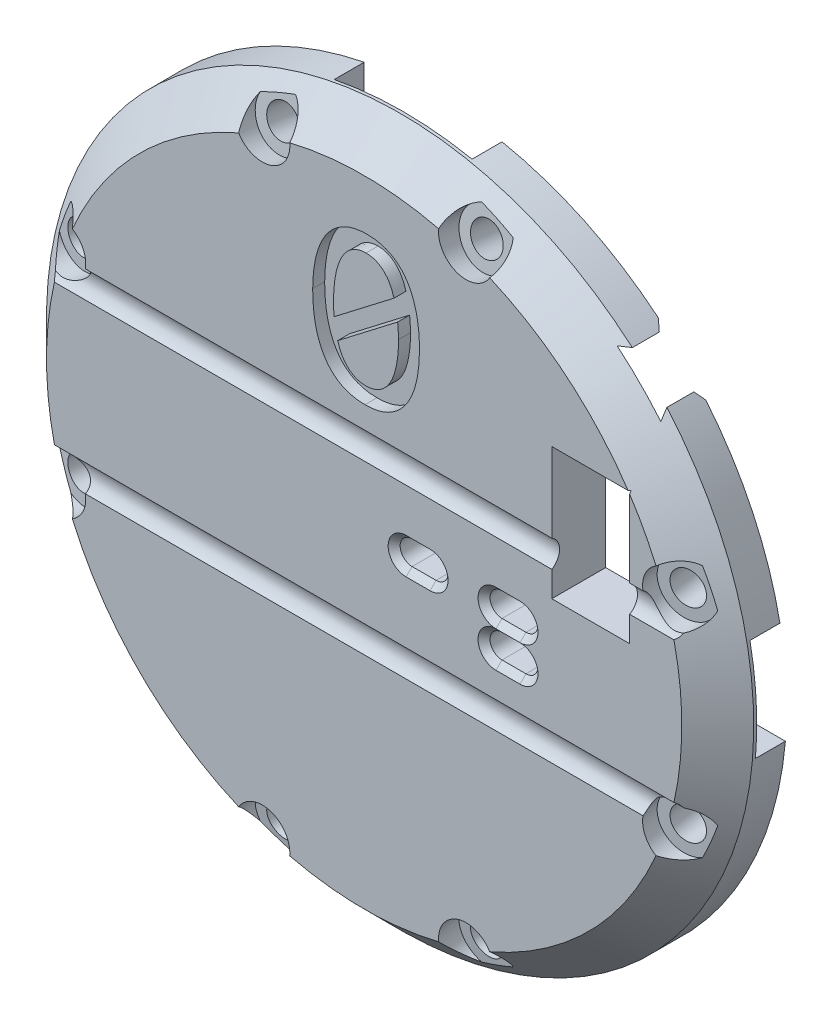
SolidWorks part; units mm, degrees
ref_plane "Front Plane" through (0, 0, 0) normal (0, 0, 1) x (1, 0, 0)
ref_plane "Top Plane" through (0, 0, 0) normal (0, 1, 0) x (1, 0, 0)
ref_plane "Right Plane" through (0, 0, 0) normal (1, 0, 0) x (0, 0, -1)
sketch "Sketch1" plane through (0, 0, 0) normal (0, 0, 1) x (1, 0, 0)
  circle A0 centre (0, 0) radius 29.5
  dimension "D1" = 59
extrude "Boss-Extrude1" add sketch "Sketch1" along normal blind 5.75
sketch "Sketch3" plane through (0, 0, 0) normal (0, 0, -1) x (-1, 0, 0)
  line L1 (-22.25, -22.25) -> (22.25, -22.25)
  line L2 (-22.25, -22.25) -> (-22.25, 22.25)
  line L3 (-22.25, 22.25) -> (22.25, 22.25)
  line L4 (22.25, -22.25) -> (22.25, 22.25)
  line L5 (-22.25, -22.25) -> (22.25, 22.25) construction
  line L6 (-22.25, 22.25) -> (22.25, -22.25) construction
  point P0 (0, 0)
  dimension "D1" = 44.5
extrude "Cut-Extrude1" cut sketch "Sketch3" against normal blind 3.25
sketch "Sketch26" plane through (0, 0, 0) normal (0, 0, -1) x (-1, 0, 0)
  line L1 (22.25, 19.3698) -> (22.25, 17.8098)
  line L2 (19.3698, -22.25) -> (17.8098, -22.25)
  line L3 (-22.25, -19.3698) -> (-22.25, -17.8098)
  line L4 (17.8098, 22.25) -> (19.3698, 22.25)
  line L6 (22.25, -17.8098) -> (22.25, -19.3698)
  line L7 (-17.8098, -22.25) -> (-19.3698, -22.25)
  arc A4 (-22.25, -19.3698) -> (-19.3698, -22.25) centre (0, 0) ccw
  arc A5 (-22.25, -17.8098) -> (-17.8098, -22.25) centre (0, 0) ccw
  arc A6 (22.25, 17.8098) -> (17.8098, 22.25) centre (0, 0) ccw
  arc A7 (22.25, 19.3698) -> (19.3698, 22.25) centre (0, 0) ccw
  arc A8 (17.8098, -22.25) -> (22.25, -17.8098) centre (0, 0) ccw
  arc A9 (19.3698, -22.25) -> (22.25, -19.3698) centre (0, 0) ccw
  dimension "D1" = 1
extrude "Boss-Extrude5" add sketch "Sketch26" against normal up to surface (3.25 mm away) up to face at (0, 0, 3.25)
chamfer "Chamfer2" distance 3 angle 45 1 edges at (29.5, 0, 5.75)
sketch "Sketch9" plane through (0, 0, 0) normal (1, 0, 0) x (0, 0, -1)
  line L0 (-26.5723, 0) -> (15.7273, 0) construction
  line L3 (-5.75, 26.5) -> (-5.75, -26.5) construction
  circle A0 centre (-6.4, 7) radius 1.3
  circle A1 centre (-6.4, -7) radius 1.3
  dimension "D1" = 2.6
  dimension "D2" = 14
  dimension "D3" = 0.65
extrude "Cut-Extrude5" cut sketch "Sketch9" against normal through all both and the other way through all
sketch "Sketch10" plane through (0, 0, 0) normal (0, 0, -1) x (-1, 0, 0)
  line L1 (22.0007, 5.75) -> (34.0342, 5.75)
  line L2 (22.0007, 5.75) -> (22.0007, -5.75)
  line L3 (22.0007, -5.75) -> (34.0342, -5.75)
  line L4 (34.0342, 5.75) -> (34.0342, -5.75)
  line L8 (-22.0007, -5.75) -> (-34.0342, -5.75)
  line L9 (-22.0007, -5.75) -> (-22.0007, 5.75)
  line L10 (-22.0007, 5.75) -> (-34.0342, 5.75)
  line L11 (-34.0342, -5.75) -> (-34.0342, 5.75)
  line L12 (-5.75, 22.0007) -> (-5.75, 34.0342)
  line L13 (-5.75, 22.0007) -> (5.75, 22.0007)
  line L14 (5.75, 22.0007) -> (5.75, 34.0342)
  line L15 (-5.75, 34.0342) -> (5.75, 34.0342)
  line L16 (5.75, -22.0007) -> (5.75, -34.0342) [skipped]
  line L17 (5.75, -22.0007) -> (-5.75, -22.0007) [skipped]
  line L18 (-5.75, -22.0007) -> (-5.75, -34.0342) [skipped]
  line L19 (5.75, -34.0342) -> (-5.75, -34.0342) [skipped]
  point P4 (22.0007, 0)
  point P21 (0, 0)
  dimension "D1" = 11.5
  dimension "D2" = 4
extrude "Cut-Extrude6" cut sketch "Sketch10" against normal blind 2.5
sketch "Sketch13" plane through (0, 0, 3.25) normal (0, 0, -1) x (-1, 0, 0)
  line L0 (-22.25, 18.5994) -> (-22.25, -17.8098) construction
  line L1 (-22.15, 14.75) -> (-15.65, 14.75)
  line L2 (-22.15, 14.75) -> (-22.15, 3.75)
  line L3 (-22.15, 3.75) -> (-15.65, 3.75)
  line L4 (-15.65, 14.75) -> (-15.65, 3.75)
  line L5 (17.8098, 22.25) -> (-18.5994, 22.25) construction
  point P23 (0, 0)
  dimension "D1" = 0.1
  dimension "D2" = 7.5
  dimension "D4" = 11
  dimension "D3" = 6.5
extrude "Cut-Extrude9" cut sketch "Sketch13" against normal through all
sketch "Sketch14" plane through (0, 0, 0) normal (0, 0, -1) x (-1, 0, 0)
  line L1 (-35.1198, 0) -> (-19.2322, 0)
  line L2 (-35.1198, 0) -> (-35.1198, -11.6)
  line L3 (-35.1198, -11.6) -> (-19.2322, -11.6)
  line L4 (-19.2322, 0) -> (-19.2322, -11.6)
  dimension "D1" = 11.6
extrude "Cut-Extrude10" cut sketch "Sketch14" against normal up to surface (2.5 mm away) up to face at (25.7335, 0, 2.5)
sketch "Sketch15" plane through (0, 0, 5.75) normal (0, 0, 1) x (1, 0, 0)
  line L0 (0, 0) -> (12.0208, 12.0208) construction
  line L1 (0, 0) -> (36.7921, 0) construction
  circle A0 centre (12.0208, 12.0208) radius 12.5
  circle A1 centre (0, 0) radius 29.5 construction
  dimension "D2" = 25
  dimension "D1" = 45
ref_axis "Axis1" through (0, 0, -0.2945) along (0, 0, 1)
ref_axis "Axis2" through (0, 31.9, 0) along (0, -1, 0)
ref_plane "Plane1" through (0, 0, 0) normal (0.1392, 0, 0.9903) x (0, -1, 0)
sketch "Sketch23" plane through (0, 0, 2.5) normal (0, 0, -1) x (-1, 0, 0)
  line L0 (-22.25, -2.55) -> (-29.3896, -2.55)
  line L1 (-22.25, -2.55) -> (-22.25, -11.6)
  line L2 (-22.25, -11.6) -> (-27.1236, -11.6)
  line L3 (-22.25, 5.75) -> (-28.9342, 5.75) construction
  arc A0 (-29.3896, -2.55) -> (-27.1236, -11.6) centre (0, 0) ccw
  arc A1 (-28.9342, 5.75) -> (-27.1236, -11.6) centre (0, 0) ccw construction
  dimension "D1" = 8.3
extrude "Boss-Extrude3" add sketch "Sketch23" along normal up to surface (2.5 mm away) up to face at (24.7749, 10.4356, 0)
sketch "Sketch17" plane through (0, 0, 0) normal (0.1392, 0, 0.9903) x (0, -1, 0)
  line L0 (0, 0) -> (0, 33.2124) construction
  line L1 (0, 0.041) -> (0, -0.8607) construction
  circle A0 centre (-8.5, 24.5) radius 1.35
  circle A1 centre (8.5, 24.5) radius 1.35
  dimension "D1" = 2.7
  dimension "D2" = 17
  dimension "D3" = 24.5
extrude "Cut-Extrude12" cut sketch "Sketch17" along normal through all
sketch "Sketch18" plane through (0, 0, 0) normal (0.1392, 0, 0.9903) x (0, -1, 0)
  circle A0 centre (-8.5, 24.5) radius 2.3
  circle A1 centre (8.5, 24.5) radius 2.3
  dimension "D1" = 4.6
extrude "Cut-Extrude13" cut sketch "Sketch18" against normal blind 12.5 from offset 20
pattern_circular "CirPattern1" count 4 over 360 about axis through (0, 0, -0.2945) along (0, 0, 1) of "Cut-Extrude12", "Cut-Extrude13"
sketch "Sketch19" plane through (0, 0, 5.75) normal (0, 0, 1) x (1, 0, 0)
  line L0 (3.5, 0.75) -> (5.5, 0.75) construction
  line L1 (3.5, 1.75) -> (5.5, 1.75)
  line L2 (3.5, -0.25) -> (5.5, -0.25)
  line L3 (11, 0.75) -> (13, 0.75) construction
  line L4 (11, 1.75) -> (13, 1.75)
  line L5 (11, -0.25) -> (13, -0.25)
  line L6 (11, -2.25) -> (13, -2.25) construction
  line L7 (11, -1.25) -> (13, -1.25)
  line L8 (11, -3.25) -> (13, -3.25)
  arc A0 (3.5, 1.75) -> (3.5, -0.25) centre (3.5, 0.75) ccw
  arc A1 (5.5, -0.25) -> (5.5, 1.75) centre (5.5, 0.75) ccw
  arc A2 (11, 1.75) -> (11, -0.25) centre (11, 0.75) ccw
  arc A3 (13, -0.25) -> (13, 1.75) centre (13, 0.75) ccw
  arc A4 (11, -1.25) -> (11, -3.25) centre (11, -2.25) ccw
  arc A5 (13, -3.25) -> (13, -1.25) centre (13, -2.25) ccw
  point P2 (4.5, 0.75)
  point P8 (12, 0.75)
  point P16 (12, -2.25)
  dimension "D1" = 1
  dimension "D2" = 3
  dimension "D3" = 7.5
  dimension "D4" = 4.5
  dimension "D5" = 2
  dimension "D6" = 0.75
extrude "Cut-Extrude14" cut sketch "Sketch19" against normal through all
sketch "Sketch21" plane through (0, 0, 3.25) normal (0, 0, -1) x (-1, 0, 0)
  line L61 (-5.5, -0.35) -> (-3.5, -0.35)
  line L62 (-3.5, 1.85) -> (-5.5, 1.85)
  line L63 (-5.5, -0.35) -> (-3.5, -0.35)
  line L64 (-3.5, 1.85) -> (-5.5, 1.85)
  line L69 (-11, 1.85) -> (-13, 1.85)
  line L70 (-13, -0.35) -> (-11, -0.35)
  line L71 (-11, 1.85) -> (-13, 1.85)
  line L72 (-13, -0.35) -> (-11, -0.35)
  line L75 (-5.5, -1.35) -> (-3.5, -1.35)
  line L76 (-3.5, 2.85) -> (-5.5, 2.85)
  line L77 (-11, -1.15) -> (-13, -1.15)
  line L78 (-13, -3.35) -> (-11, -3.35)
  line L79 (-11, -1.15) -> (-13, -1.15)
  line L80 (-13, -3.35) -> (-11, -3.35)
  line L81 (-11, 2.85) -> (-13, 2.85)
  line L84 (-13, -4.35) -> (-11, -4.35)
  line L85 (-13, -1.35) -> (-11, -1.35) construction
  line L86 (-11, -0.15) -> (-13, -0.15) construction
  arc A55 (-5.5, 1.85) -> (-5.5, -0.35) centre (-5.5, 0.75) ccw
  arc A56 (-3.5, -0.35) -> (-3.5, 1.85) centre (-3.5, 0.75) ccw
  arc A57 (-5.5, 1.85) -> (-5.5, -0.35) centre (-5.5, 0.75) ccw
  arc A58 (-3.5, -0.35) -> (-3.5, 1.85) centre (-3.5, 0.75) ccw
  arc A65 (-13, 1.85) -> (-13, -0.35) centre (-13, 0.75) ccw
  arc A66 (-11, -0.35) -> (-11, 1.85) centre (-11, 0.75) ccw
  arc A67 (-13, 1.85) -> (-13, -0.35) centre (-13, 0.75) ccw
  arc A68 (-11, -0.35) -> (-11, 1.85) centre (-11, 0.75) ccw
  arc A73 (-5.5, 2.85) -> (-5.5, -1.35) centre (-5.5, 0.75) ccw
  arc A74 (-3.5, -1.35) -> (-3.5, 2.85) centre (-3.5, 0.75) ccw
  arc A75 (-13, -1.15) -> (-13, -3.35) centre (-13, -2.25) ccw
  arc A76 (-11, -3.35) -> (-11, -1.15) centre (-11, -2.25) ccw
  arc A77 (-13, -1.15) -> (-13, -3.35) centre (-13, -2.25) ccw
  arc A78 (-11, -3.35) -> (-11, -1.15) centre (-11, -2.25) ccw
  arc A80 (-13, 2.85) -> (-14.4697, -0.75) centre (-13, 0.75) ccw
  arc A81 (-11, -4.35) -> (-9.5303, -0.75) centre (-11, -2.25) ccw
  arc A84 (-9.5303, -0.75) -> (-11, 2.85) centre (-11, 0.75) ccw
  arc A85 (-11, -4.35) -> (-11, -0.15) centre (-11, -2.25) ccw construction
  arc A86 (-14.4697, -0.75) -> (-13, -4.35) centre (-13, -2.25) ccw
  arc A87 (-11, -1.35) -> (-11, 2.85) centre (-11, 0.75) ccw construction
  arc A88 (-13, 2.85) -> (-13, -1.35) centre (-13, 0.75) ccw construction
  arc A90 (-13, -0.15) -> (-13, -4.35) centre (-13, -2.25) ccw construction
  dimension "D1" = 0.1
  dimension "D2" = 0.1
  dimension "D3" = 0.1
  dimension "D4" = 1
  dimension "D5" = 1
extrude "Boss-Extrude2" add sketch "Sketch21" along normal blind 2
fillet "Fillet1" radius 1 7 edges at (7.6, 0.75, 3.25) (4.5, 2.85, 3.25) (1.4, 0.75, 3.25) (14.9442, -3.0437, 3.25) (9.0558, -3.0437, 3.25) (4.5, -1.35, 3.25) (12, -4.35, 3.25)
sketch "Sketch24" plane through (0, 0, 5.75) normal (0, 0, 1) x (1, 0, 0)
  line L0 (-5.1692, 10.1499) -> (12.5197, 10.1499) construction
  line L1 (0, 0) -> (0, 40.6298) construction
  text T0 "0" font "Consolas" height in points 46
extrude "Cut-Extrude16" cut sketch "Sketch24" against normal blind 1
sketch "Sketch25" plane through (0, 0, 3.25) normal (0, 0, -1) x (-1, 0, 0)
  line L0 (-22.25, 15.75) -> (-22.25, 14.75)
  line L1 (-22.25, 5.75) -> (-22.25, 19.3698) construction
  line L2 (-22.25, 14.75) -> (-15.65, 14.75)
  line L3 (-15.65, 14.75) -> (-15.65, 3.75)
  line L4 (-15.65, 3.75) -> (-22.25, 3.75)
  line L5 (-22.25, -2.55) -> (-22.25, 5.75) construction
  line L6 (-22.25, 3.75) -> (-22.25, 2.75)
  line L7 (-22.25, 2.75) -> (-14.65, 2.75)
  line L8 (-14.65, 2.75) -> (-14.65, 15.75)
  line L9 (-14.65, 15.75) -> (-22.25, 15.75)
  dimension "D1" = 1
  dimension "D2" = 1
  dimension "D3" = 1
extrude "Boss-Extrude4" add sketch "Sketch25" along normal blind 2
chamfer "Chamfer3" distance 0.5 angle 45 3 edges at (18.45, 15.75, 1.25) (18.45, 2.75, 1.25) (14.65, 9.25, 1.25)
chamfer "Chamfer4" distance 0.5 angle 45 12 edges at (10, 0.75, 5.75) (12, -0.25, 5.75) (12, 1.75, 5.75) (14, 0.75, 5.75) (12, -3.25, 5.75) (14, -2.25, 5.75) (10, -2.25, 5.75) (12, -1.25, 5.75) (2.5, 0.75, 5.75) (4.5, -0.25, 5.75) (4.5, 1.75, 5.75) (6.5, 0.75, 5.75)
chamfer "Chamfer5" distance 0.5 angle 45 7 edges at (-22.25, 11.7799, 0) (-22.25, -11.7799, 0) (0, -22.25, 0) (22.25, -10.1799, 0) (22.25, 12.5599, 0) (-11.7799, 22.25, 0) (12.5599, 22.25, 0)
